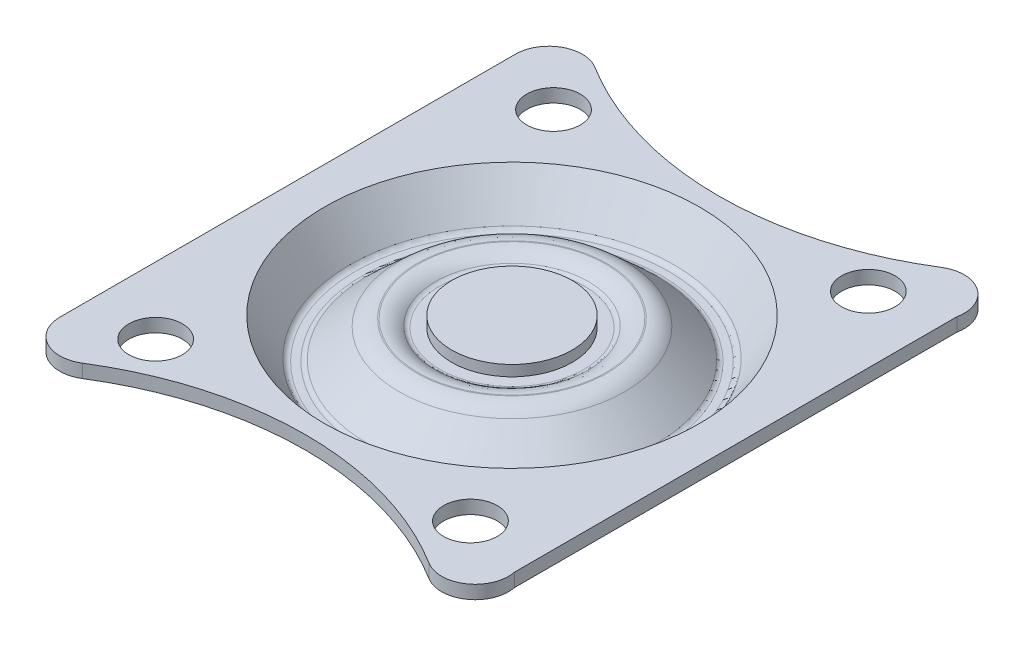
SolidWorks part; units mm, degrees
ref_plane "Alzado" through (0, 0, 0) normal (0, 0, 1) x (1, 0, 0)
ref_plane "Planta" through (0, 0, 0) normal (0, 1, 0) x (1, 0, 0)
ref_plane "Vista lateral" through (0, 0, 0) normal (1, 0, 0) x (0, 0, -1)
sketch "Croquis1" plane through (0, 0, 0) normal (0, 1, 0) x (1, 0, 0)
  line L0 (0, 15.4257) -> (17.2343, 15.4257) construction
  line L2 (-16.75, -17) -> (-16.75, 17)
  line L4 (16.6995, -16.5) -> (16.6995, 16.5)
  line L5 (-16.75, -19) -> (16.75, 19) construction
  line L6 (-16.75, 19) -> (16.75, -19) construction
  line L7 (0, 0) -> (16.75, 0) construction
  line L8 (0, 0) -> (0, 22.221) construction
  arc A0 (-12.9285, 19.1222) -> (12.9285, 19.1222) centre (0, 39.8828) ccw
  arc A1 (-12.9285, 19.1222) -> (-16.75, 17) centre (-14.25, 17) ccw
  arc A2 (12.9285, 19.1222) -> (16.6995, 16.5) centre (14.25, 17) cw
  arc A3 (-12.9285, -19.1222) -> (12.9285, -19.1222) centre (0, -39.8828) cw
  arc A4 (-12.9285, -19.1222) -> (-16.75, -17) centre (-14.25, -17) cw
  arc A5 (12.9285, -19.1222) -> (16.6995, -16.5) centre (14.25, -17) ccw
  circle A6 centre (-11.75, -14.85) radius 2
  circle A7 centre (-11.75, 14.85) radius 2
  circle A8 centre (11.75, -14.85) radius 2
  circle A9 centre (11.75, 14.85) radius 2
  point P0 (0, 0)
  dimension "D3" = 29.7
  dimension "D4" = 5
  dimension "D5" = 4
  dimension "D6" = 5
  dimension "D7" = 33
  dimension "D8" = 23.5
  dimension "D1" = 33.5
  dimension "D2" = 38
extrude "Extruir1" add sketch "Croquis1" along normal blind 1
sketch "Croquis2" plane through (0, 1, 0) normal (0, 1, 0) x (1, 0, 0)
  circle A0 centre (0, 0) radius 4
  dimension "D1" = 8
sketch "Croquis4" plane through (0, 1, 0) normal (0, 1, 0) x (1, 0, 0)
  circle A0 centre (0, 0) radius 14
  dimension "D1" = 28
extrude "Extruir3" cut sketch "Croquis4" against normal through all
sketch "Croquis3" plane through (0, 0, 0) normal (0, 0, 1) x (1, 0, 0)
  line L0 (-12.9285, 0) -> (12.9285, 0) construction
  line L1 (-14.5277, 0) -> (-12.4767, -3)
  line L2 (-10.5625, -3) -> (-12.4767, -3)
  line L3 (-5.949, 0.8) -> (-5.75, 0.2)
  line L4 (12.9285, 1) -> (-12.9285, 1) construction
  line L5 (-10.5625, -3) -> (-7.4816, -0.2)
  line L6 (-7.4816, -0.2) -> (-6.6709, -0.2)
  line L7 (-10.949, -2) -> (-7.8682, 0.8)
  line L8 (-7.8682, 0.8) -> (-5.949, 0.8)
  line L9 (-12.949, -0.5373) -> (-11.949, -2)
  line L10 (-10.949, -2) -> (-11.949, -2)
  line L11 (-6.6709, -0.2) -> (-6.4719, -0.8)
  line L12 (-6.4719, -0.8) -> (0, -0.8)
  line L13 (0, -0.8) -> (0, 0.2)
  line L14 (0, 0.2) -> (0, 12.6983) construction
  line L15 (-14, 1) -> (-14, 0)
  line L17 (-12.949, -0.5373) -> (-14, 1)
  line L18 (-13.7745, -1.1017) -> (-12.4767, -3) construction
  line L19 (-16.75, 0) -> (-12.9285, 0) construction
  line L20 (-5.75, 0.2) -> (0, 0.2)
  line L21 (14, 1) -> (-14, 1) construction
  line L23 (-14, 0) -> (-14.5277, 0)
  dimension "D1" = 2
  dimension "D2" = 5.75
  dimension "D3" = 5
  dimension "D4" = 1
  dimension "D5" = 0.2
  dimension "D6" = 2
  dimension "D7" = 1
revolve "Revolución1" add sketch "Croquis3" angle 360 about L14
fillet "Redondeo1" radius 2 2 edges at (0, -3, -10.5625) (0, -3, -12.4767)
fillet "Redondeo2" radius 0.5 3 edges at (0, -2, -11.949) (0, 0.2, -5.75) (0, -2, -10.949)
fillet "Redondeo3" radius 2 2 edges at (0, 0.8, -5.949) (0, 0.8, -7.8682)
extrude "Extruir5" cut sketch "Croquis2" against normal through all
sketch "Croquis5" plane through (0, 1, 0) normal (0, 1, 0) x (1, 0, 0)
  circle A0 centre (0, 0) radius 4.5
  dimension "D1" = 9
extrude "Extruir6" add sketch "Croquis5" against normal blind 6
sketch "Croquis6" plane through (0, -5, 0) normal (0, -1, 0) x (1, 0, 0)
  circle A0 centre (0, 0) radius 5
  dimension "D1" = 10
extrude "Extruir7" add sketch "Croquis6" along normal blind 1
fillet "Redondeo7" radius 0.5 1 edges at (0, -6, -5)
sketch "Croquis7" plane through (0, 0, 0) normal (0, 0, 1) x (1, 0, 0)
  line L0 (-7.5801, -0.4418) -> (-7.5801, -3.4418)
  arc A0 (-7.5801, -0.4418) -> (-7.5801, -3.4418) centre (-7.5801, -1.9418) ccw
  dimension "D1" = 1.5
revolve "Revolución2" add sketch "Croquis7" angle 360 about L0
ref_axis "Eje2" through (0, -6.35, 0) along (0, 1, 0)
pattern_circular "MatrizC3" count 16 over 360 about axis through (0, -6.35, 0) along (0, 1, 0) of bodies 111
